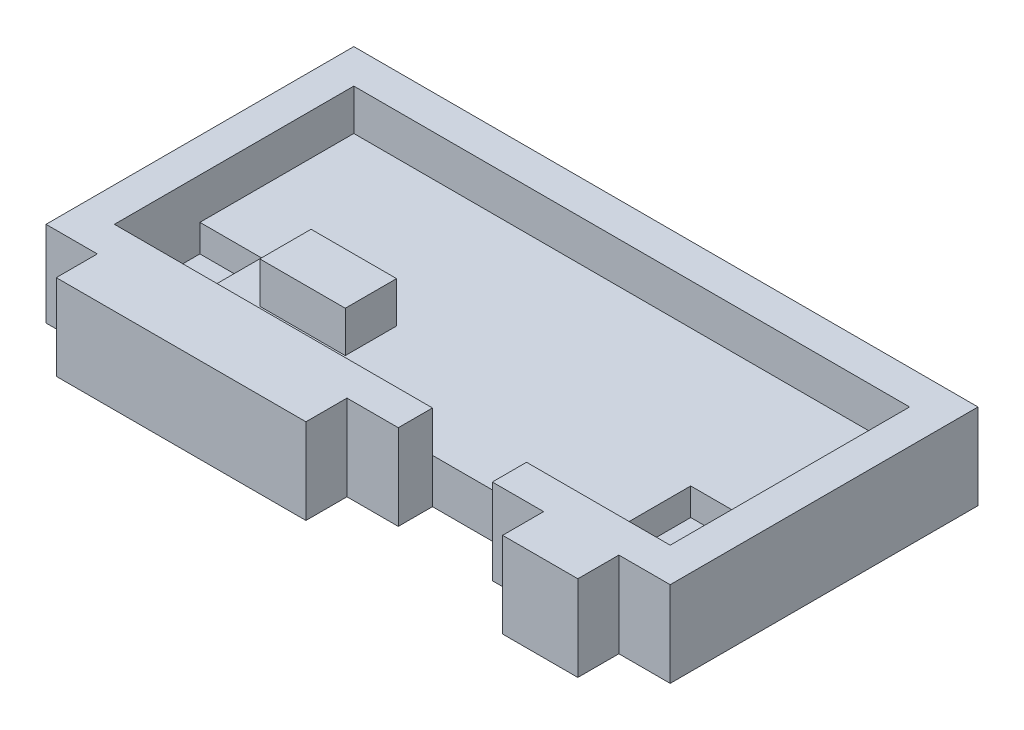
SolidWorks part; units mm, degrees
ref_plane "Front Plane" through (0, 0, 0) normal (0, 0, 1) x (1, 0, 0)
ref_plane "Top Plane" through (0, 0, 0) normal (0, 1, 0) x (1, 0, 0)
ref_plane "Right Plane" through (0, 0, 0) normal (1, 0, 0) x (0, 0, -1)
sketch "Sketch1" plane through (0, 0, 0) normal (0, 1, 0) x (1, 0, 0)
  line L1 (0, 0) -> (36.5, 0)
  line L2 (0, 0) -> (0, 18)
  line L3 (0, 18) -> (36.5, 18)
  line L4 (36.5, 0) -> (36.5, 18)
  dimension "D1" = 36.5
  dimension "D2" = 18
extrude "Boss-Extrude1" add sketch "Sketch1" against normal blind 5
sketch "Sketch2" plane through (0, 0, 0) normal (0, 1, 0) x (1, 0, 0)
  line L0 (36.5, 18) -> (0, 18) construction
  line L1 (2, 16) -> (34.5, 16)
  line L2 (2, 16) -> (2, 2)
  line L3 (2, 2) -> (34.5, 2)
  line L4 (34.5, 16) -> (34.5, 2)
  line L5 (0, 18) -> (0, 0) construction
  line L6 (0, 0) -> (36.5, 0) construction
  line L7 (36.5, 0) -> (36.5, 18) construction
  dimension "D1" = 2
  dimension "D2" = 2
  dimension "D3" = 2
  dimension "D4" = 2
extrude "Cut-Extrude1" cut sketch "Sketch2" against normal blind 2.4
sketch "Sketch3" plane through (0, -2.4, 0) normal (0, 1, 0) x (1, 0, 0)
  line L0 (34.5, 16) -> (2, 16) construction
  line L1 (8, 7.5) -> (13, 7.5)
  line L2 (8, 7.5) -> (8, 4.5)
  line L3 (8, 4.5) -> (13, 4.5)
  line L4 (13, 7.5) -> (13, 4.5)
  line L5 (2, 16) -> (2, 2) construction
  dimension "D1" = 3
  dimension "D2" = 8.5
  dimension "D3" = 5
  dimension "D4" = 6
extrude "Boss-Extrude2" add sketch "Sketch3" along normal blind 2.4
sketch "Sketch4" plane through (0, 0, -2) normal (0, 0, -1) x (-1, 0, 0)
  line L0 (-36.5, 0) -> (0, 0) construction
  line L1 (-26.1, 0) -> (-20.6, 0)
  line L2 (-26.1, 0) -> (-26.1, -5)
  line L3 (-26.1, -5) -> (-20.6, -5)
  line L4 (-20.6, 0) -> (-20.6, -5)
  line L5 (-36.5, -5) -> (-36.5, 0) construction
  dimension "D1" = 10.4
  dimension "D2" = 5.5
  dimension "D3" = 5
extrude "Cut-Extrude2" cut sketch "Sketch4" against normal up to next
sketch "Sketch5" plane through (0, -2.4, 0) normal (0, 1, 0) x (1, 0, 0)
  line L0 (2, 16) -> (2, 2) construction
  line L1 (2, 7) -> (5.6, 7)
  line L2 (2, 7) -> (2, 2)
  line L3 (2, 2) -> (5.6, 2)
  line L4 (5.6, 7) -> (5.6, 2)
  line L5 (2, 2) -> (20.6, 2) construction
  line L7 (34.5, 2) -> (29.7, 2)
  line L8 (34.5, 2) -> (34.5, 8)
  line L9 (34.5, 8) -> (29.7, 8)
  line L10 (29.7, 2) -> (29.7, 8)
  dimension "D1" = 3.6
  dimension "D2" = 5
  dimension "D3" = 0
  dimension "D4" = 6
  dimension "D5" = 4.8
extrude "Cut-Extrude3" cut sketch "Sketch5" against normal blind 1.6
sketch "Sketch6" plane through (0, 0, 0) normal (0, 0, 1) x (1, 0, 0)
  line L0 (0, 0) -> (20.6, 0) construction
  line L1 (3, 0) -> (17.6, 0)
  line L2 (3, 0) -> (3, -5)
  line L3 (3, -5) -> (17.6, -5)
  line L4 (17.6, 0) -> (17.6, -5)
  line L5 (0, -5) -> (20.6, -5) construction
  line L6 (0, -5) -> (0, 0) construction
  line L7 (20.6, -5) -> (20.6, 0) construction
  line L8 (26.1, 0) -> (36.5, 0) construction
  line L9 (29.1, 0) -> (33.5, 0)
  line L10 (29.1, 0) -> (29.1, -5)
  line L11 (29.1, -5) -> (33.5, -5)
  line L12 (33.5, 0) -> (33.5, -5)
  line L13 (26.1, -5) -> (36.5, -5) construction
  line L14 (36.5, -5) -> (36.5, 0) construction
  line L15 (26.1, 0) -> (26.1, -5) construction
  dimension "D1" = 3
  dimension "D2" = 3
  dimension "D3" = 3
  dimension "D4" = 3
extrude "Boss-Extrude3" add sketch "Sketch6" along normal blind 2.4
